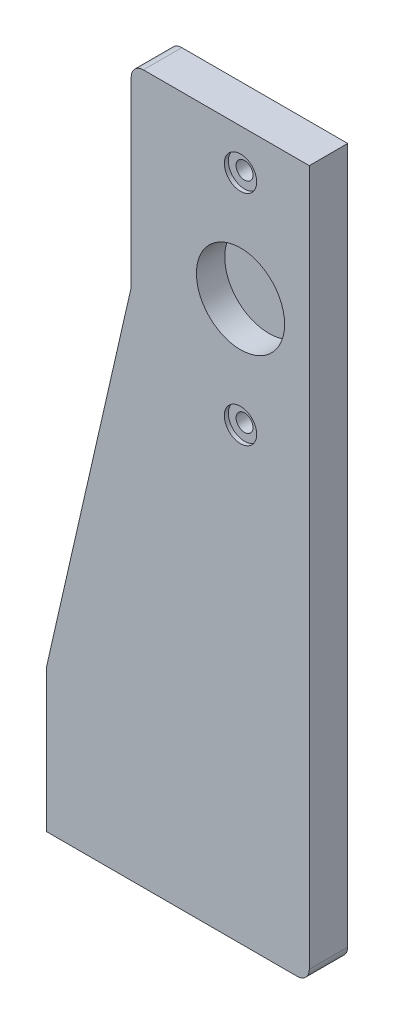
SolidWorks part; units mm, degrees
ref_plane "前视基准面" through (0, 0, 0) normal (0, 0, 1) x (1, 0, 0)
ref_plane "上视基准面" through (0, 0, 0) normal (0, 1, 0) x (1, 0, 0)
ref_plane "右视基准面" through (0, 0, 0) normal (1, 0, 0) x (0, 0, -1)
sketch "草图10" plane through (0, 0, 0) normal (0, 0, 1) x (1, 0, 0)
  line L0 (0, 0) -> (65, 0)
  line L1 (65, 0) -> (65, 175)
  line L2 (65, 175) -> (21, 175)
  line L3 (21, 175) -> (21, 127)
  line L4 (21, 127) -> (0, 35)
  line L5 (0, 35) -> (0, 0)
  line L6 (49, 175) -> (49, 0) construction
  dimension "D1" = 65
  dimension "D2" = 175
  dimension "D3" = 44
  dimension "D4" = 48
  dimension "D5" = 35
  dimension "D6" = 16
extrude "凸台-拉伸4" add sketch "草图10" along normal blind 9.5 contours L4 L5 L0 L1 L2 L3
sketch "草图11" plane through (0, 0, 9.5) normal (0, 0, 1) x (1, 0, 0)
  line L0 (48, 175) -> (48, 0) construction
  line L1 (65, 175) -> (21, 175) construction
  line L2 (0, 0) -> (65, 0) construction
  line L3 (65, 0) -> (65, 175) construction
  circle A0 centre (48, 165) radius 2.1
  circle A1 centre (48, 111) radius 2.1
  dimension "D1" = 4.2
  dimension "D2" = 10
  dimension "D3" = 54
  dimension "D4" = 17
extrude "切除-拉伸8" cut sketch "草图11" against normal through all contours A1 | A0
sketch "草图12" plane through (0, 0, 9.5) normal (0, 0, 1) x (1, 0, 0)
  circle A0 centre (48, 165) radius 4
  circle A1 centre (48, 111) radius 4
  dimension "D1" = 8
extrude "切除-拉伸9" cut sketch "草图12" against normal blind 1
fillet "圆角7" radius 3 3 edges at (65, 0, 4.75) (21, 127, 4.75) (21, 175, 4.75)
sketch "草图13" plane through (0, 0, 9.5) normal (0, 0, 1) x (1, 0, 0)
  line L0 (48, 165) -> (48, 51.4877) construction
sketch "草图19" plane through (0, 0, 9.5) normal (0, 0, 1) x (1, 0, 0)
  circle A1 centre (48, 138) radius 10.9
  dimension "D1" = 21.8
extrude "切除-拉伸11" cut sketch "草图19" against normal blind 7
